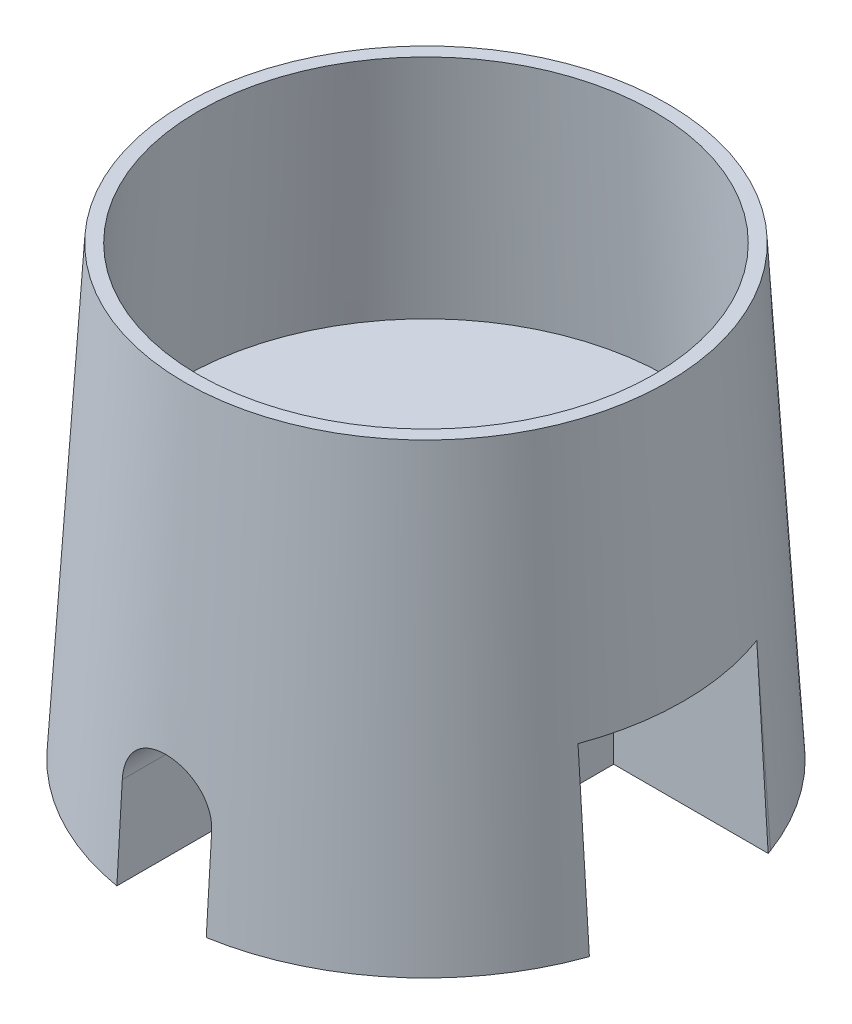
SolidWorks part; units mm, degrees
ref_plane "前视基准面" through (0, 0, 0) normal (0, 0, 1) x (1, 0, 0)
ref_plane "上视基准面" through (0, 0, 0) normal (0, 1, 0) x (1, 0, 0)
ref_plane "右视基准面" through (0, 0, 0) normal (1, 0, 0) x (0, 0, -1)
sketch "草图3" plane through (0, 0, 0) normal (1, 0, 0) x (0, 0, -1)
  line L0 (0, 0) -> (60, 0)
  line L1 (60, 0) -> (54, 100)
  line L2 (54, 100) -> (0, 100)
  line L3 (0, 100) -> (0, 0)
  dimension "D1" = 100
  dimension "D2" = 54
  dimension "D3" = 60
revolve "旋转2" add sketch "草图3" angle 360 about L3
sketch "草图5" plane through (0, 0, 0) normal (0, -1, 0) x (-1, 0, 0)
  line L0 (0, 0) -> (0, 71.9204) construction
  line L1 (0, 0) -> (72.7838, 0) construction
  line L3 (20, -30) -> (-20, -30)
  line L4 (20, -30) -> (20, 30)
  line L5 (20, 30) -> (-20, 30)
  line L6 (-20, -30) -> (-20, 30)
  dimension "D1" = 60
  dimension "D2" = 40
extrude "切除-拉伸1" cut sketch "草图5" against normal blind 40
sketch "草图6" plane through (0, 0, 0) normal (1, 0, 0) x (0, 0, -1)
  line L0 (0, 0) -> (0, 62.3248) construction
  line L1 (-60, 0) -> (60, 0) construction
  line L2 (-20, 0) -> (20, 0)
  line L3 (-20, 0) -> (-20, 40)
  line L4 (-20, 40) -> (20, 40)
  line L5 (20, 0) -> (20, 40)
  dimension "D1" = 40
  dimension "D2" = 40
extrude "切除-拉伸2" cut sketch "草图6" against normal blind 40 from offset 22 offset against normal yes
sketch "草图9" plane through (0, 0, 0) normal (1, 0, 0) x (0, 0, -1)
  line L0 (0, 0) -> (0, 62.3248) construction
  line L2 (-20, 0) -> (20, 0)
  line L3 (-20, 0) -> (-20, 40)
  line L4 (-20, 40) -> (20, 40)
  line L5 (20, 0) -> (20, 40)
  dimension "D1" = 40
  dimension "D2" = 40
extrude "切除-拉伸3" cut sketch "草图9" along normal blind 40 from offset 22
sketch "草图10" plane through (0, 0, 30) normal (0, 0, -1) x (-1, 0, 0)
  line L0 (0, 0) -> (0, 41.5034) construction
  line L1 (-10, 0) -> (-10, 20)
  line L2 (-56.5685, 0) -> (56.5685, 0) construction
  line L3 (-10, 0) -> (10, 0)
  line L4 (10, 0) -> (10, 20)
  arc A0 (-10, 20) -> (10, 20) centre (0, 20) cw
  dimension "D3" = 10
  dimension "D1" = 10
  dimension "D2" = 20
extrude "切除-拉伸4" cut sketch "草图10" against normal blind 40
sketch "草图11" plane through (0, 0, 0) normal (0, 0, 1) x (1, 0, 0)
  line L0 (-50.9946, 100) -> (-54.1746, 47)
  line L1 (54, 100) -> (-54, 100) construction
  line L2 (-54.1746, 47) -> (0, 47)
  line L3 (0, 47) -> (0, 100)
  line L4 (0, 100) -> (-50.9946, 100)
  line L5 (-54, 100) -> (-57.6, 40) construction
  dimension "D1" = 53
  dimension "D2" = 3
revolve "切除-旋转1" cut sketch "草图11" angle 360 about L3
hole_wizard "Ø2.5mm 暗销孔1" positions "草图14" profile "草图15" hole size "Ø2.5" standard "ISO" end condition through all
sketch "草图14" plane through (0, 47, 0) normal (0, 1, 0) x (1, 0, 0)
  line L0 (0, 0) -> (97.1322, 0) construction
  line L2 (0, 0) -> (0, -66.7943) construction
  point P17 (-10.5, 13.5)
  point P21 (-10.5, -13.5)
  point P22 (41.5, 13.5)
  point P32 (41.5, -13.5)
  dimension "D1" = 13.5
  dimension "D2" = 10.5
  dimension "D3" = 52
  dimension "D4" = 13.5
sketch "草图15" plane through (41.5, 47, 13.5) normal (1, 0, 0) x (0, 0, 1)
  line L0 (0, 0) -> (0, 47)
  line L1 (0, 47) -> (1.25, 47)
  line L2 (1.25, 47) -> (1.25, 0.025)
  line L3 (1.25, 0.025) -> (1.275, 0)
  line L5 (1.275, 0) -> (0, 0)
  line L6 (-1.25, 0.025) -> (-1.275, 0) construction
  line L11 (0, -6.35) -> (0, 107.95) construction
  dimension "通孔孔直径" = 2.5
  dimension "通孔孔深度" = 47
  dimension "近端锥形沉头孔直径" = 2.55
  dimension "近端锥形沉头孔角度" = 90
